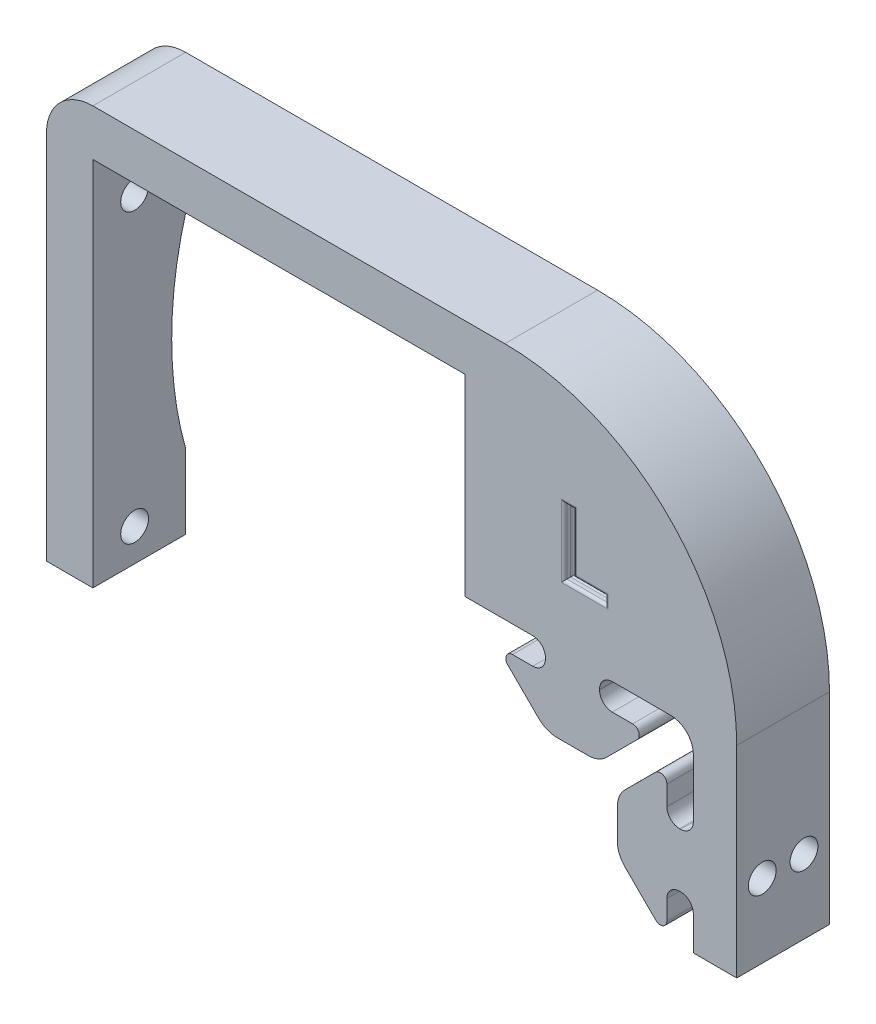
SolidWorks part; units mm, degrees
ref_plane "Front Plane" through (0, 0, 0) normal (0, 0, 1) x (1, 0, 0)
ref_plane "Top Plane" through (0, 0, 0) normal (0, 1, 0) x (1, 0, 0)
ref_plane "Right Plane" through (0, 0, 0) normal (1, 0, 0) x (0, 0, -1)
sketch "Sketch1" plane through (0, 0, 0) normal (0, 0, 1) x (1, 0, 0)
  line L0 (13.02, -7.9417) -> (17.7, -7.9417)
  line L1 (17.7, -7.9417) -> (17.7, 38.77)
  line L2 (17.7, 38.77) -> (-56.7, 38.77)
  line L3 (-14.4742, -8.23) -> (-67.0037, -8.23) construction
  line L4 (-19.4439, -8.23) -> (-19.4439, 33.77) construction
  line L5 (-10.5664, 13.02) -> (-10.5664, 33.77)
  line L6 (-10.5664, 33.77) -> (-51.7, 33.77)
  line L7 (-51.7, 33.77) -> (-51.7, -6.23)
  line L8 (-56.7, 38.77) -> (-56.7, -6.23)
  line L9 (-56.7, -6.23) -> (-51.7, -6.23)
  line L10 (12.7, -6.3331) -> (12.7, -7.9417) construction
  line L11 (13.02, -5.3171) -> (13.02, -4.2875)
  line L12 (11.651, -2.9185) -> (11.5392, -2.9185)
  line L13 (10.1702, -4.2875) -> (10.1702, -6.4021)
  line L14 (8.9631, -6.9029) -> (5.667, -3.6143)
  line L15 (4.8285, -1.5932) -> (4.8285, 1.5932)
  line L16 (5.667, 3.6143) -> (8.9631, 6.9029)
  line L17 (10.1702, 6.4021) -> (10.1702, 4.2875)
  line L18 (11.5392, 2.9185) -> (11.651, 2.9185)
  line L19 (13.02, 10.5773) -> (13.02, 4.2875)
  line L20 (6.3329, 13.02) -> (10.5626, 13.0198)
  line L22 (6.3329, 13.02) -> (4.2875, 13.02)
  line L23 (2.9185, 11.651) -> (2.9185, 11.5392)
  line L24 (4.2875, 10.1702) -> (6.4768, 10.1702)
  line L25 (6.981, 8.9509) -> (3.6723, 5.6497)
  line L26 (1.6558, 4.8158) -> (-1.6558, 4.8158)
  line L27 (-3.6723, 5.6497) -> (-6.981, 8.9509)
  line L28 (-6.4768, 10.1702) -> (-4.2875, 10.1702)
  line L29 (-2.9185, 11.5392) -> (-2.9185, 11.651)
  line L30 (-4.2875, 13.02) -> (-5.3171, 13.02)
  line L31 (-5.3171, 13.02) -> (-10.5664, 13.02)
  line L32 (13.02, -5.3171) -> (13.02, -7.9417)
  line L33 (13.02, -6.3331) -> (13.02, -7.9417) construction
  line L34 (13.02, 4.2875) -> (13.02, 5.3171) construction
  line L37 (5.3171, 13.02) -> (4.2875, 13.02) construction
  line L38 (-6.3331, 13.02) -> (-9.5504, 13.02) construction
  line L96 (12.7, -5.3171) -> (12.7, -4.2875) construction
  line L97 (11.651, -3.2385) -> (11.5392, -3.2385) construction
  line L98 (10.4902, -4.2875) -> (10.4902, -6.4021) construction
  line L99 (8.7371, -7.1294) -> (5.441, -3.8408) construction
  line L100 (4.5085, -1.5932) -> (4.5085, 1.5932) construction
  line L101 (5.441, 3.8408) -> (8.7371, 7.1294) construction
  line L102 (10.4902, 6.4021) -> (10.4902, 4.2875) construction
  line L103 (11.5392, 3.2385) -> (11.651, 3.2385) construction
  line L104 (12.7, 4.2875) -> (12.7, 5.3171) construction
  line L105 (12.7, 6.3331) -> (12.7, 9.5504) construction
  line L106 (9.5504, 12.7) -> (6.3331, 12.7) construction
  line L107 (5.3171, 12.7) -> (4.2875, 12.7) construction
  line L108 (3.2385, 11.651) -> (3.2385, 11.5392) construction
  line L109 (4.2875, 10.4902) -> (6.4768, 10.4902) construction
  line L110 (7.207, 8.7244) -> (3.8983, 5.4232) construction
  line L111 (1.6558, 4.4958) -> (-1.6558, 4.4958) construction
  line L112 (-3.8983, 5.4232) -> (-7.207, 8.7244) construction
  line L113 (-6.4768, 10.4902) -> (-4.2875, 10.4902) construction
  line L114 (-3.2385, 11.5392) -> (-3.2385, 11.651) construction
  line L115 (-4.2875, 12.7) -> (-5.3171, 12.7) construction
  line L116 (-6.3331, 12.7) -> (-9.5504, 12.7) construction
  arc A0 (13.02, -4.2875) -> (11.651, -2.9185) centre (11.651, -4.2875) ccw
  arc A1 (11.5392, -2.9185) -> (10.1702, -4.2875) centre (11.5392, -4.2875) ccw
  arc A2 (8.9631, -6.9029) -> (10.1702, -6.4021) centre (9.4628, -6.4021) ccw
  arc A3 (4.8285, -1.5932) -> (5.667, -3.6143) centre (7.6835, -1.5932) ccw
  arc A4 (5.667, 3.6143) -> (4.8285, 1.5932) centre (7.6835, 1.5932) ccw
  arc A5 (10.1702, 6.4021) -> (8.9631, 6.9029) centre (9.4628, 6.4021) ccw
  arc A6 (10.1702, 4.2875) -> (11.5392, 2.9185) centre (11.5392, 4.2875) ccw
  arc A7 (11.651, 2.9185) -> (13.02, 4.2875) centre (11.651, 4.2875) ccw
  arc A8 (4.2875, 13.02) -> (2.9185, 11.651) centre (4.2875, 11.651) ccw
  arc A9 (2.9185, 11.5392) -> (4.2875, 10.1702) centre (4.2875, 11.5392) ccw
  arc A10 (6.981, 8.9509) -> (6.4768, 10.1702) centre (6.4768, 9.4563) ccw
  arc A11 (1.6558, 4.8158) -> (3.6723, 5.6497) centre (1.6558, 7.6708) ccw
  arc A12 (-3.6723, 5.6497) -> (-1.6558, 4.8158) centre (-1.6558, 7.6708) ccw
  arc A13 (-6.4768, 10.1702) -> (-6.981, 8.9509) centre (-6.4768, 9.4563) ccw
  arc A14 (-4.2875, 10.1702) -> (-2.9185, 11.5392) centre (-4.2875, 11.5392) ccw
  arc A15 (-2.9185, 11.651) -> (-4.2875, 13.02) centre (-4.2875, 11.651) ccw
  arc A16 (13.02, 10.5773) -> (10.5626, 13.0198) centre (10.5918, 10.5918) ccw
  arc A17 (13.0198, 10.5625) -> (10.5626, 13.0198) centre (10.5918, 10.5918) ccw construction
  arc A114 (12.7, -5.3171) -> (12.7, -6.3331) centre (12.7, -5.8251) ccw construction
  arc A115 (12.7, -4.2875) -> (11.651, -3.2385) centre (11.651, -4.2875) ccw construction
  arc A116 (11.5392, -3.2385) -> (10.4902, -4.2875) centre (11.5392, -4.2875) ccw construction
  arc A117 (8.7371, -7.1294) -> (10.4902, -6.4021) centre (9.4628, -6.4021) ccw construction
  arc A118 (4.5085, -1.5932) -> (5.441, -3.8408) centre (7.6835, -1.5932) ccw construction
  arc A119 (5.441, 3.8408) -> (4.5085, 1.5932) centre (7.6835, 1.5932) ccw construction
  arc A120 (10.4902, 6.4021) -> (8.7371, 7.1294) centre (9.4628, 6.4021) ccw construction
  arc A121 (10.4902, 4.2875) -> (11.5392, 3.2385) centre (11.5392, 4.2875) ccw construction
  arc A122 (11.651, 3.2385) -> (12.7, 4.2875) centre (11.651, 4.2875) ccw construction
  arc A123 (12.7, 6.3331) -> (12.7, 5.3171) centre (12.7, 5.8251) ccw construction
  arc A124 (12.6998, 10.5664) -> (12.7, 9.5504) centre (12.7, 10.0584) ccw construction
  arc A125 (12.6998, 10.5664) -> (10.5664, 12.6998) centre (10.5918, 10.5918) ccw construction
  arc A126 (9.5504, 12.7) -> (10.5664, 12.6998) centre (10.0584, 12.7) ccw construction
  arc A127 (5.3171, 12.7) -> (6.3331, 12.7) centre (5.8251, 12.7) ccw construction
  arc A128 (4.2875, 12.7) -> (3.2385, 11.651) centre (4.2875, 11.651) ccw construction
  arc A129 (3.2385, 11.5392) -> (4.2875, 10.4902) centre (4.2875, 11.5392) ccw construction
  arc A130 (7.207, 8.7244) -> (6.4768, 10.4902) centre (6.4768, 9.4563) ccw construction
  arc A131 (1.6558, 4.4958) -> (3.8983, 5.4232) centre (1.6558, 7.6708) ccw construction
  arc A132 (-3.8983, 5.4232) -> (-1.6558, 4.4958) centre (-1.6558, 7.6708) ccw construction
  arc A133 (-6.4768, 10.4902) -> (-7.207, 8.7244) centre (-6.4768, 9.4563) ccw construction
  arc A134 (-4.2875, 10.4902) -> (-3.2385, 11.5392) centre (-4.2875, 11.5392) ccw construction
  arc A135 (-3.2385, 11.651) -> (-4.2875, 12.7) centre (-4.2875, 11.651) ccw construction
  arc A136 (-6.3331, 12.7) -> (-5.3171, 12.7) centre (-5.8251, 12.7) ccw construction
  arc A137 (-10.5664, 12.6998) -> (-9.5504, 12.7) centre (-10.0584, 12.7) ccw construction
  dimension "D1" = 47
  dimension "D2" = 74.4
  dimension "D3" = 5
  dimension "D4" = 5
  dimension "D5" = 40
  dimension "D6" = 5
  dimension "D8" = 0.32
  dimension "D7" = 6.2898
  dimension "D9" = 4.2297
  dimension "D10" = 20.75
extrude "Boss-Extrude1" add sketch "Sketch1" along normal blind 10
sketch "Sketch2" plane through (-56.7, 0, 0) normal (-1, 0, 0) x (0, 0, 1)
  line L1 (10, 38.77) -> (0, 38.77) construction
  line L2 (10, 29.3002) -> (10, -6.23) construction
  line L7 (5.5, 28.27) -> (5.5, -2.73) construction
  circle A0 centre (5.5, -2.73) radius 1.5
  circle A1 centre (5.5, 28.27) radius 1.5
  dimension "D3" = 3
  dimension "D4" = 3
  dimension "D1" = 4.5
  dimension "D2" = 31
  dimension "D5" = 10.5
extrude "Cut-Extrude1" cut sketch "Sketch2" against normal up to next
fillet "Fillet3" radius 5 1 edges at (-56.7, 38.77, 5)
sketch "Sketch3" plane through (17.7, 0, 0) normal (1, 0, 0) x (0, 0, -1)
  line L0 (-5, 1.5932) -> (-5, -1.5932) construction
  line L1 (-10, 0) -> (0, 0) construction
  line L4 (0, -1.5932) -> (0, 1.5932)
  line L5 (-10, -1.5932) -> (0, -1.5932)
  line L6 (-10, 1.5932) -> (-10, -1.5932)
  line L7 (0, 1.5932) -> (-10, 1.5932)
  line L12 (0, -1.5932) -> (0, 1.5932) construction
  line L13 (-10, -1.5932) -> (0, -1.5932) construction
  line L14 (-10, 1.5932) -> (-10, -1.5932) construction
  line L15 (0, 1.5932) -> (-10, 1.5932) construction
  circle A0 centre (-7.25, 0) radius 1.5
  circle A1 centre (-2.75, 0) radius 1.5
  dimension "D4" = 2.25
  dimension "D2" = 3
  dimension "D3" = 2.25
  dimension "D1" = 0
extrude "Cut-Extrude2" cut sketch "Sketch3" against normal up to next contours A1 | A0
fillet "Fillet4" radius 25 1 edges at (17.7, 38.77, 5)
sketch "Sketch7" plane through (0, 0, 10) normal (0, 0, 1) x (1, 0, 0)
  text T0 "L" font "Arial" height in points 28
extrude "Cut-Extrude7" cut sketch "Sketch7" against normal blind 1
fillet "Fillet8" radius 0.3 12 edges at (-0.901, 23.4386, 9) (-0.3939, 27.0343, 9) (0.1132, 23.8535, 9) (1.8188, 20.6728, 9) (3.5244, 20.2579, 9) (1.3117, 19.843, 9) (1.3117, 19.843, 10) (3.5244, 20.2579, 10) (1.8188, 20.6728, 10) (0.1132, 23.8535, 10) (-0.3939, 27.0343, 10) (-0.901, 23.4386, 10)
sketch "Sketch8" plane through (-10.5664, 0, 0) normal (-1, 0, 0) x (0, 0, 1)
  line L4 (0, 33.77) -> (0, 13.02)
  line L5 (0, 13.02) -> (10, 13.02)
  line L6 (10, 13.02) -> (10, 33.77)
  line L7 (10, 33.77) -> (0, 33.77)
  line L8 (0, 33.77) -> (0, 13.02)
  line L9 (0, 13.02) -> (10, 13.02)
  line L10 (10, 13.02) -> (10, 33.77)
  line L11 (10, 33.77) -> (0, 33.77)
  dimension "D1" = 0
extrude "Boss-Extrude2" add sketch "Sketch8" along normal blind 1
sketch "Sketch10" plane through (0, 0, 0) normal (0, 0, -1) x (-1, 0, 0)
  line L0 (51.7, -1.23) -> (51.7, -4.23) construction
  line L1 (51.7, 29.77) -> (51.7, 26.77) construction
  line L2 (51.7, -1.23) -> (51.7, -4.23) construction
  line L3 (51.7, 29.77) -> (51.7, 26.77) construction
  line L4 (51.7, 28.27) -> (51.7, -2.73) construction
  line L6 (49.7, 1.77) -> (53.7, 1.77)
  line L7 (49.7, 1.77) -> (49.7, 23.77)
  line L8 (49.7, 23.77) -> (53.7, 23.77)
  line L9 (53.7, 1.77) -> (53.7, 23.77)
  line L10 (49.7, 1.77) -> (53.7, 23.77) construction
  line L11 (49.7, 23.77) -> (53.7, 1.77) construction
  point P6 (51.7, 12.77)
  dimension "D1" = 22
  dimension "D2" = 2
extrude "Cut-Extrude9" cut sketch "Sketch10" against normal blind 1.5
fillet "Fillet10" radius 40 2 edges at (-52.7, 1.77, 1.5) (-52.7, 23.77, 1.5)
